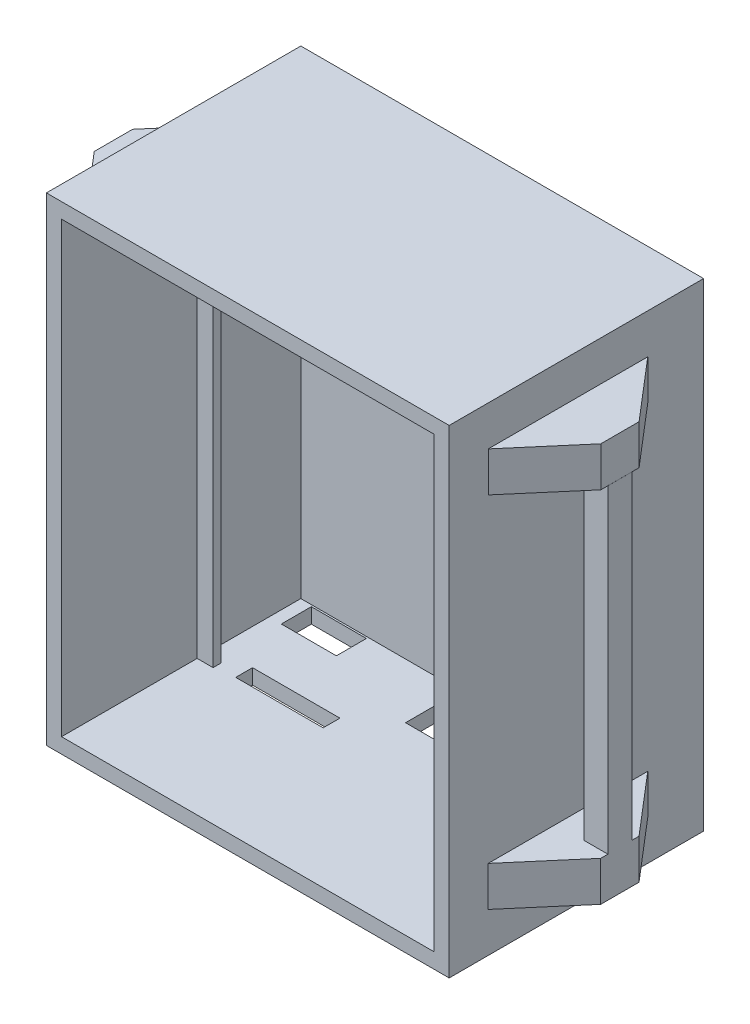
SolidWorks part; units mm, degrees
ref_plane "Piano frontale" through (0, 0, 0) normal (0, 0, 1) x (1, 0, 0)
ref_plane "Piano superiore" through (0, 0, 0) normal (0, 1, 0) x (1, 0, 0)
ref_plane "Piano destro" through (0, 0, 0) normal (1, 0, 0) x (0, 0, -1)
sketch "Schizzo1" plane through (0, 0, 0) normal (0, 0, 1) x (1, 0, 0)
  line L1 (0, 0) -> (50.5, 0)
  line L2 (0, 0) -> (0, 60)
  line L3 (0, 60) -> (50.5, 60)
  line L4 (50.5, 0) -> (50.5, 60)
  dimension "D1" = 50.5
  dimension "D2" = 60
extrude "Estrusione-Estrusione1" add sketch "Schizzo1" along normal blind 1.9
sketch "Schizzo2" plane through (0, 0, 1.9) normal (0, 0, 1) x (1, 0, 0)
  line L0 (0, 0) -> (50.5, 0) construction
  line L1 (0, 60) -> (1.9, 60)
  line L2 (0, 60) -> (0, 0)
  line L3 (0, 0) -> (1.9, 0)
  line L4 (1.9, 60) -> (1.9, 0)
  dimension "D1" = 1.9
extrude "Estrusione-Estrusione2" add sketch "Schizzo2" along normal blind 30
sketch "Schizzo3" plane through (0, 0, 1.9) normal (0, 0, 1) x (1, 0, 0)
  line L0 (50.5, 0) -> (50.5, 60) construction
  line L1 (1.9, 0) -> (50.5, 0)
  line L2 (1.9, 0) -> (1.9, 1.9)
  line L3 (1.9, 1.9) -> (50.5, 1.9)
  line L4 (50.5, 0) -> (50.5, 1.9)
  dimension "D1" = 1.9
extrude "Estrusione-Estrusione3" add sketch "Schizzo3" along normal blind 30
sketch "Schizzo4" plane through (0, 0, 1.9) normal (0, 0, 1) x (1, 0, 0)
  line L0 (50.5, 60) -> (1.9, 60) construction
  line L1 (50.5, 1.9) -> (48.6, 1.9)
  line L2 (50.5, 1.9) -> (50.5, 60)
  line L3 (50.5, 60) -> (48.6, 60)
  line L4 (48.6, 1.9) -> (48.6, 60)
  dimension "D1" = 1.9
extrude "Estrusione-Estrusione4" add sketch "Schizzo4" along normal blind 30
sketch "Schizzo5" plane through (0, 0, 1.9) normal (0, 0, 1) x (1, 0, 0)
  line L0 (48.6, 60) -> (48.6, 1.9) construction
  line L1 (1.9, 60) -> (48.6, 60)
  line L2 (1.9, 60) -> (1.9, 58.1)
  line L3 (1.9, 58.1) -> (48.6, 58.1)
  line L4 (48.6, 60) -> (48.6, 58.1)
  dimension "D1" = 1.9
extrude "Estrusione-Estrusione5" add sketch "Schizzo5" along normal blind 30
sketch "Schizzo6" plane through (0, 0, 1.9) normal (0, 0, 1) x (1, 0, 0)
  line L0 (48.6, 40.9769) -> (44, 40.9769)
  line L1 (48.6, 58.1) -> (48.6, 1.9) construction
  line L2 (44, 40.9769) -> (44, 1.9)
  line L3 (48.6, 1.9) -> (1.9, 1.9) construction
  line L4 (44, 1.9) -> (48.6, 1.9)
  line L5 (48.6, 1.9) -> (48.6, 40.9769)
  dimension "D1" = 4.6
extrude "Estrusione-Estrusione6" add sketch "Schizzo6" along normal blind 13
sketch "Schizzo7" plane through (0, 0, 1.9) normal (0, 0, 1) x (1, 0, 0)
  line L0 (1.9, 1.9) -> (1.9, 58.1) construction
  line L1 (1.9, 43.9691) -> (25.3766, 43.9691)
  line L2 (1.9, 43.9691) -> (1.9, 48.629)
  line L3 (1.9, 48.629) -> (25.3766, 48.629)
  line L4 (25.3766, 43.9691) -> (25.3766, 48.629)
extrude "Estrusione-Estrusione7" add sketch "Schizzo7" along normal blind 13
sketch "Schizzo8" plane through (1.9, 0, 0) normal (1, 0, 0) x (0, 0, -1)
  line L0 (-31.9, 1.9) -> (-1.9, 1.9) construction
  line L1 (-14.9, 43.9691) -> (-13.9, 43.9691)
  line L2 (-14.9, 43.9691) -> (-14.9, 1.9)
  line L3 (-14.9, 1.9) -> (-13.9, 1.9)
  line L4 (-13.9, 43.9691) -> (-13.9, 1.9)
  dimension "D1" = 1
extrude "Estrusione-Estrusione8" add sketch "Schizzo8" along normal blind 2
sketch "Schizzo9" plane through (48.6, 0, 0) normal (-1, 0, 0) x (0, 0, 1)
  line L0 (31.9, 58.1) -> (1.9, 58.1) construction
  line L1 (14.9, 40.9769) -> (13.4, 40.9769)
  line L2 (14.9, 40.9769) -> (14.9, 58.1)
  line L3 (14.9, 58.1) -> (13.4, 58.1)
  line L4 (13.4, 40.9769) -> (13.4, 58.1)
  dimension "D1" = 1.5
extrude "Estrusione-Estrusione9" add sketch "Schizzo9" along normal blind 4
sketch "Schizzo10" plane through (1.9, 0, 0) normal (1, 0, 0) x (0, 0, -1)
  line L0 (-31.9, 58.1) -> (-1.9, 58.1) construction
  line L1 (-14.9, 48.629) -> (-13.4, 48.629)
  line L2 (-14.9, 48.629) -> (-14.9, 58.1)
  line L3 (-14.9, 58.1) -> (-13.4, 58.1)
  line L4 (-13.4, 48.629) -> (-13.4, 58.1)
  dimension "D1" = 1.5
extrude "Estrusione-Estrusione10" add sketch "Schizzo10" along normal blind 4
sketch "Schizzo11" plane through (0, 0, 0) normal (0, -1, 0) x (-1, 0, 0)
  line L1 (-3.4392, -5.8852) -> (-10.3444, -5.8852)
  line L2 (-3.4392, -5.8852) -> (-3.4392, -2.1208)
  line L3 (-3.4392, -2.1208) -> (-10.3444, -2.1208)
  line L4 (-10.3444, -5.8852) -> (-10.3444, -2.1208)
extrude "Taglio-Estrusione1" cut sketch "Schizzo11" against normal blind 2
sketch "Schizzo13" plane through (0, 0, 0) normal (0, -1, 0) x (-1, 0, 0)
  line L1 (-37.8471, -8.8172) -> (-21.9434, -8.8172)
  line L2 (-37.8471, -8.8172) -> (-37.8471, -3.9519)
  line L3 (-37.8471, -3.9519) -> (-21.9434, -3.9519)
  line L4 (-21.9434, -8.8172) -> (-21.9434, -3.9519)
extrude "Taglio-Estrusione2" cut sketch "Schizzo13" against normal blind 2
sketch "Schizzo14" plane through (0, 0, 0) normal (0, -1, 0) x (1, 0, 0)
  line L1 (6.3759, 14.5379) -> (17.3347, 14.5379)
  line L2 (6.3759, 14.5379) -> (6.3759, 12.4313)
  line L3 (6.3759, 12.4313) -> (17.3347, 12.4313)
  line L4 (17.3347, 14.5379) -> (17.3347, 12.4313)
extrude "Taglio-Estrusione3" cut sketch "Schizzo14" against normal blind 2
sketch "Schizzo15" plane through (50.5, 0, 0) normal (1, 0, 0) x (0, 0, -1)
  line L4 (-27.0015, 4.9955) -> (-7.0015, 4.9955)
  line L5 (-27.0015, 4.9955) -> (-27.0015, 9.9955)
  line L6 (-27.0015, 9.9955) -> (-7.0015, 9.9955)
  line L7 (-7.0015, 4.9955) -> (-7.0015, 9.9955)
  dimension "D1" = 20
  dimension "D2" = 5
extrude "Estrusione-Estrusione11" add sketch "Schizzo15" along normal blind 6.5
sketch "Schizzo16" plane through (0, 9.9955, 0) normal (0, 1, 0) x (1, 0, 0)
  line L1 (57, -7.0015) -> (57, -27.0015) construction
  line L3 (57, -18.502) -> (54, -18.502)
  line L4 (57, -18.502) -> (57, -15.502)
  line L5 (57, -15.502) -> (54, -15.502)
  line L6 (54, -18.502) -> (54, -15.502)
  dimension "D1" = 3
  dimension "D2" = 3
extrude "Estrusione-Estrusione12" add sketch "Schizzo16" along normal blind 40
sketch "Schizzo17" plane through (50.5, 0, 0) normal (1, 0, 0) x (0, 0, -1)
  line L4 (-26.9989, 55.0015) -> (-6.9989, 55.0015)
  line L5 (-26.9989, 55.0015) -> (-26.9989, 50.0015)
  line L6 (-26.9989, 50.0015) -> (-6.9989, 50.0015)
  line L7 (-6.9989, 55.0015) -> (-6.9989, 50.0015)
  dimension "D1" = 20
  dimension "D2" = 5
extrude "Estrusione-Estrusione13" add sketch "Schizzo17" along normal blind 6.5
sketch "Schizzo18" plane through (0, 4.9955, 0) normal (0, -1, 0) x (1, 0, 0)
  line L0 (57, 27.0015) -> (50.5, 27.0015)
  line L1 (50.5, 27.0015) -> (57, 19.3963)
  line L2 (57, 27.0015) -> (57, 7.0015) construction
  line L3 (57, 19.3963) -> (57, 27.0015)
extrude "Taglio-Estrusione4" cut sketch "Schizzo18" against normal blind 6.5
sketch "Schizzo19" plane through (0, 4.9955, 0) normal (0, -1, 0) x (1, 0, 0)
  line L0 (57, 7.0015) -> (50.5, 7.0015)
  line L1 (50.5, 7.0015) -> (57, 14.5977)
  line L2 (57, 19.3963) -> (57, 7.0015) construction
  line L3 (57, 14.5977) -> (57, 7.0015)
extrude "Taglio-Estrusione5" cut sketch "Schizzo19" against normal blind 6.5
sketch "Schizzo20" plane through (0, 55.0015, 0) normal (0, 1, 0) x (1, 0, 0)
  line L0 (57, -26.9989) -> (50.5, -26.9989)
  line L1 (50.5, -26.9989) -> (57, -19.3895)
  line L2 (57, -6.9989) -> (57, -26.9989) construction
  line L3 (57, -19.3895) -> (57, -26.9989)
extrude "Taglio-Estrusione6" cut sketch "Schizzo20" against normal blind 6.5
sketch "Schizzo21" plane through (0, 55.0015, 0) normal (0, 1, 0) x (1, 0, 0)
  line L0 (57, -6.9989) -> (50.5, -6.9989)
  line L1 (50.5, -6.9989) -> (57, -14.5918)
  line L2 (57, -6.9989) -> (57, -19.3895) construction
  line L3 (57, -14.5918) -> (57, -6.9989)
extrude "Taglio-Estrusione7" cut sketch "Schizzo21" against normal blind 6.5
sketch "Schizzo22" plane through (0, 0, 0) normal (-1, 0, 0) x (0, 0, 1)
  line L4 (26.9963, 5.0038) -> (6.995, 5.0038)
  line L5 (26.9963, 5.0038) -> (26.9963, 10.0038)
  line L6 (26.9963, 10.0038) -> (6.995, 10.0038)
  line L7 (6.995, 5.0038) -> (6.995, 10.0038)
  dimension "D1" = 5
extrude "Estrusione-Estrusione14" add sketch "Schizzo22" along normal blind 6.5
sketch "Schizzo23" plane through (0, 10.0038, 0) normal (0, 1, 0) x (1, 0, 0)
  line L1 (-6.5, -26.9963) -> (-6.5, -6.995) construction
  line L3 (-6.5, -18.4992) -> (-3.5, -18.4992)
  line L4 (-6.5, -18.4992) -> (-6.5, -15.4992)
  line L5 (-6.5, -15.4992) -> (-3.5, -15.4992)
  line L6 (-3.5, -18.4992) -> (-3.5, -15.4992)
  dimension "D1" = 3
  dimension "D2" = 3
extrude "Estrusione-Estrusione15" add sketch "Schizzo23" along normal blind 40
sketch "Schizzo24" plane through (0, 0, 0) normal (-1, 0, 0) x (0, 0, 1)
  line L4 (27.0022, 55.0005) -> (6.9989, 55.0005)
  line L5 (27.0022, 55.0005) -> (27.0022, 50.0005)
  line L6 (27.0022, 50.0005) -> (6.9989, 50.0005)
  line L7 (6.9989, 55.0005) -> (6.9989, 50.0005)
  dimension "D1" = 5
extrude "Estrusione-Estrusione16" add sketch "Schizzo24" along normal blind 6.5
sketch "Schizzo25" plane through (0, 5.0038, 0) normal (0, -1, 0) x (-1, 0, 0)
  line L0 (6.5, -6.995) -> (0, -6.995)
  line L1 (0, -6.995) -> (6.5, -14.5889)
  line L2 (6.5, -6.995) -> (6.5, -26.9963) construction
  line L3 (6.5, -14.5889) -> (6.5, -6.995)
extrude "Taglio-Estrusione8" cut sketch "Schizzo25" against normal blind 6.5
sketch "Schizzo26" plane through (0, 5.0038, 0) normal (0, -1, 0) x (-1, 0, 0)
  line L0 (6.5, -26.9963) -> (0, -26.9963)
  line L1 (0, -26.9963) -> (6.5, -19.4014)
  line L2 (6.5, -14.5889) -> (6.5, -26.9963) construction
  line L3 (6.5, -19.4014) -> (6.5, -26.9963)
extrude "Taglio-Estrusione9" cut sketch "Schizzo26" against normal blind 6.5
sketch "Schizzo27" plane through (0, 55.0005, 0) normal (0, 1, 0) x (1, 0, 0)
  line L0 (-6.5, -27.0022) -> (0, -27.0022)
  line L1 (0, -27.0022) -> (-6.5, -19.4014)
  line L2 (-6.5, -19.4014) -> (-6.5, -27.0022)
extrude "Taglio-Estrusione10" cut sketch "Schizzo27" against normal blind 6.5
sketch "Schizzo28" plane through (0, 55.0005, 0) normal (0, 1, 0) x (1, 0, 0)
  line L0 (-6.5, -6.9989) -> (0, -6.9989)
  line L1 (0, -6.9989) -> (-6.5, -14.5889)
  line L2 (-6.5, -14.5889) -> (-6.5, -6.9989)
extrude "Taglio-Estrusione11" cut sketch "Schizzo28" against normal blind 6.5
